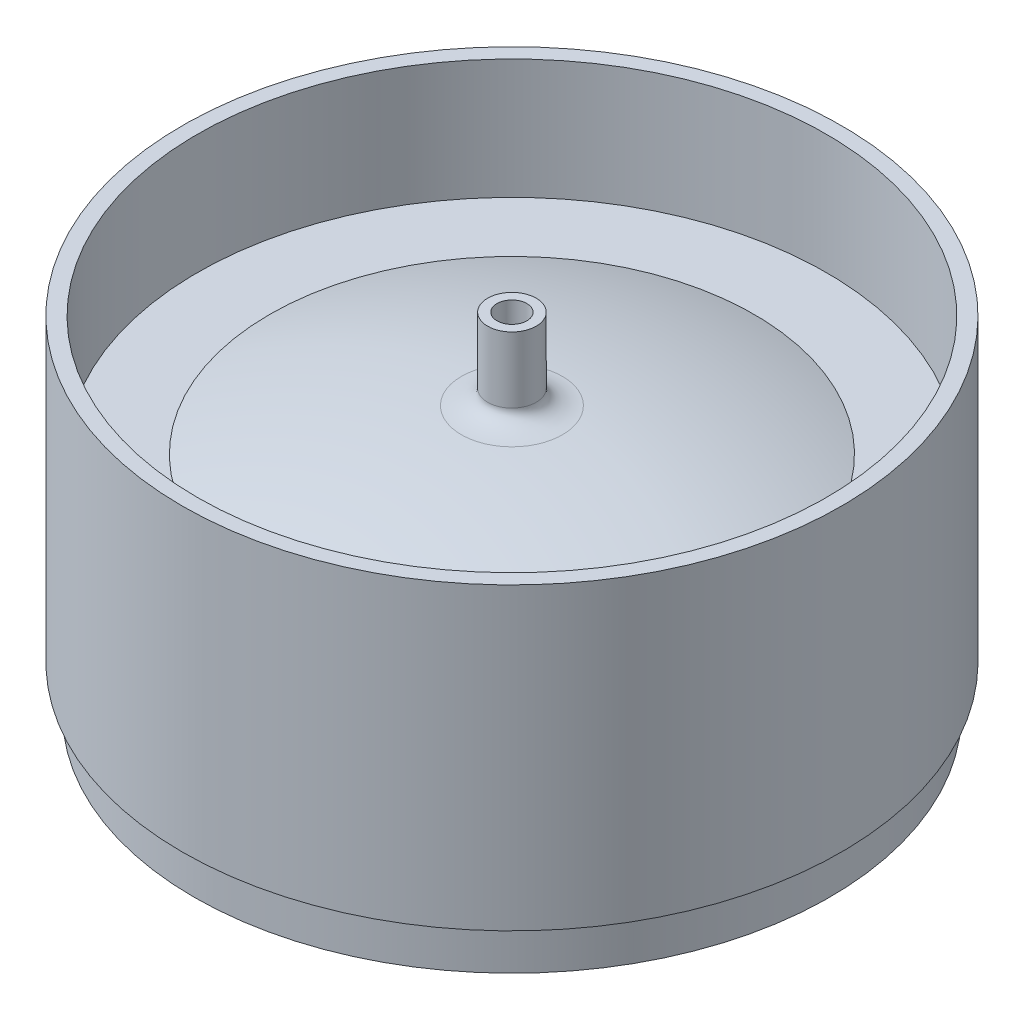
SolidWorks part; units mm, degrees
material "6061-T6 (SS)"
ref_plane "Front Plane" through (0, 0, 0) normal (0, 0, 1) x (1, 0, 0)
ref_plane "Top Plane" through (0, 0, 0) normal (0, 1, 0) x (1, 0, 0)
ref_plane "Right Plane" through (0, 0, 0) normal (1, 0, 0) x (0, 0, -1)
ref_axis "Axis1" through (0, 127.061, 0) along (0, -1, 0)
sketch "Sketch1" plane through (0, 0, 0) normal (0, 0, 1) x (1, 0, 0)
  line L0 (-69.85, 9.525) -> (-69.85, 73.025)
  line L2 (0, 127.061) -> (0, -81.9141) construction
  line L3 (-69.85, 9.525) -> (-67.3735, 9.525)
  line L4 (-67.3735, 9.525) -> (-67.3735, 0)
  line L5 (-67.3735, 0) -> (-65.786, 0)
  line L6 (55, 0) -> (-55, 0) construction
  line L7 (-66.675, 73.025) -> (-69.85, 73.025)
  line L9 (-66.675, 47.625) -> (-51.3431, 47.625)
  line L11 (-66.675, 47.625) -> (-66.675, 73.025)
  line L12 (-5.1435, 59.7286) -> (-5.1435, 73.6986)
  line L13 (-5.1435, 73.6986) -> (-3.175, 73.6986)
  line L14 (-3.175, 73.6986) -> (-3.175, 50.5611)
  line L15 (-65.786, 0) -> (-65.786, 9.525)
  line L16 (-65.786, 9.525) -> (-63.3918, 23.1034)
  arc A0 (-63.3918, 23.1034) -> (-51.3431, 40.8202) centre (-44.3418, 23.1034) cw
  arc A1 (-51.3431, 40.8202) -> (-3.175, 50.5611) centre (0, -89.1028) cw
  arc A3 (-51.3431, 47.625) -> (-10.7155, 56.5536) centre (0, -89.1028) cw
  spline S0 degree 3 poles (-5.1435, 59.7286) (-5.1435, 57.4599) (-8.5179, 56.7153) (-10.7155, 56.5536) knots 0 0 0 0 1 1 1 1
  point P14 (-66.5797, 0)
  dimension "D5" = 19.05
  dimension "D6" = 139.7
  dimension "D7" = 146.05
  dimension "D8" = 63.5
  dimension "D2" = 170
  dimension "D3" = 9.525
  dimension "D4" = 1.5875
  dimension "D9" = 25.4
  dimension "D10" = 3.175
  dimension "D11" = 5.1435
  dimension "D12" = 3.175
  dimension "D13" = 13.97
  dimension "D14" = 3.175
  dimension "D15" = 4.064
  dimension "D16" = 69.85
revolve "Revolve1" add sketch "Sketch1" angle 360 about axis through (0, 127.061, 0) along (0, -1, 0)
